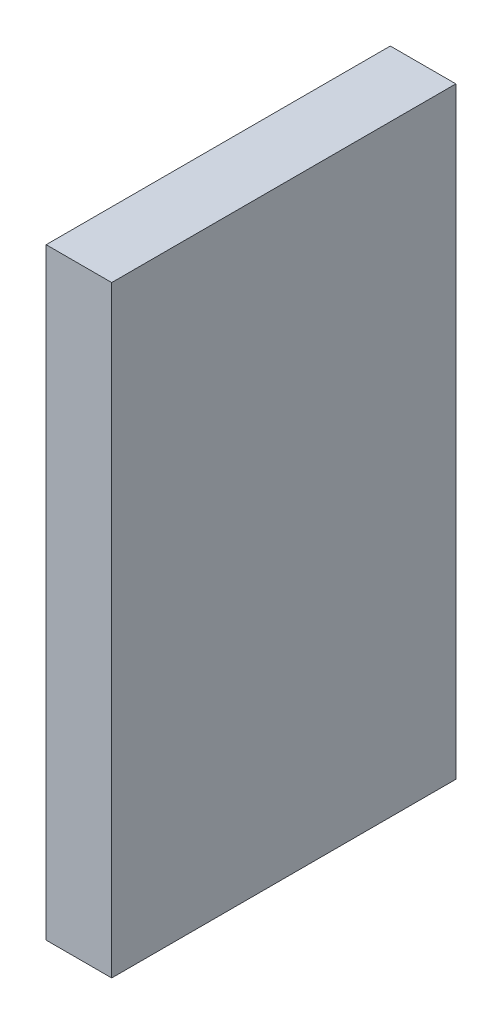
SolidWorks part; units mm, degrees
ref_plane "Front Plane" through (0, 0, 0) normal (0, 0, 1) x (1, 0, 0)
ref_plane "Top Plane" through (0, 0, 0) normal (0, 1, 0) x (1, 0, 0)
ref_plane "Right Plane" through (0, 0, 0) normal (1, 0, 0) x (0, 0, -1)
sketch "Sketch1" plane through (0, 0, 0) normal (0, 0, 1) x (1, 0, 0)
  line L2 (215, -300) -> (234.05, -300)
  line L3 (300, -300) -> (-300, -300) construction
  line L4 (234.05, -300) -> (234.05, -125)
  line L6 (215, -300) -> (215, -125) construction
  line L7 (215, -300) -> (215, -125)
  line L8 (215, -125) -> (234.05, -125)
extrude "Boss-Extrude1" add sketch "Sketch1" along normal up to surface (100 mm away)
